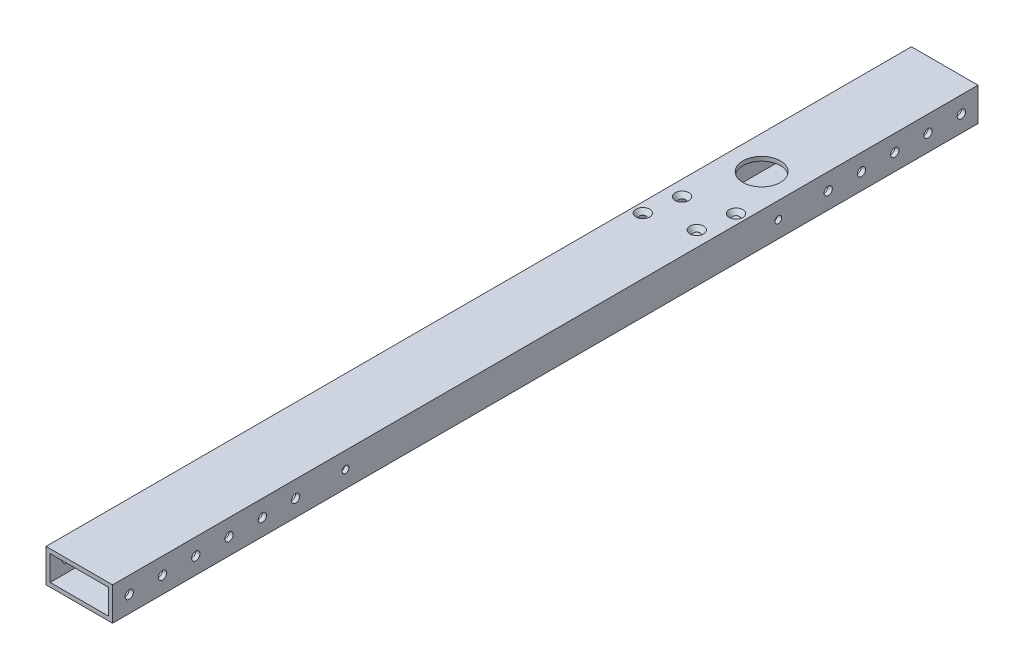
SolidWorks part; units mm, degrees
material "6061 Alloy"
ref_plane "Front Plane" through (0, 0, 0) normal (0, 0, 1) x (1, 0, 0)
ref_plane "Top Plane" through (0, 0, 0) normal (0, 1, 0) x (1, 0, 0)
ref_plane "Right Plane" through (0, 0, 0) normal (1, 0, 0) x (0, 0, -1)
sketch "Sketch1" plane through (0, 0, 0) normal (0, 0, 1) x (1, 0, 0)
  line L0 (-22.225, 9.525) -> (22.225, 9.525)
  line L2 (-25.4, 12.7) -> (25.4, 12.7)
  line L3 (-25.4, 12.7) -> (-25.4, -12.7)
  line L4 (-25.4, -12.7) -> (25.4, -12.7)
  line L5 (25.4, 12.7) -> (25.4, -12.7)
  line L10 (22.225, 9.525) -> (22.225, -9.525)
  line L11 (-22.225, -9.525) -> (22.225, -9.525)
  line L12 (-22.225, 9.525) -> (-22.225, -9.525)
  point P12 (0, 12.7)
  point P14 (25.4, 0)
  dimension "Wall Thickness" = 3.175
  dimension "Outside Width" = 50.8
  dimension "Outside Height" = 25.4
  dimension "Inside Height" = 19.05
  dimension "Inside Width" = 44.45
sketch "Sketch2" plane through (0, 0, 0) normal (1, 0, 0) x (0, 0, -1)
  line L0 (330.2, 0) -> (-330.2, 0)
  point P4 (0, 0)
  point P7 (-330.2, 0)
  point P10 (330.2, 0)
  dimension "Length" = 660.4
sketch "Sketch3" plane through (0, 0, 0) normal (0, 0, 1) x (1, 0, 0)
  line L21 (25.4, 12.7) -> (-25.4, 12.7)
  line L22 (25.4, -12.7) -> (25.4, 12.7)
  line L23 (-25.4, -12.7) -> (25.4, -12.7)
  line L24 (-25.4, 12.7) -> (-25.4, -12.7)
  line L25 (25.4, 12.7) -> (-25.4, 12.7)
  line L26 (25.4, -12.7) -> (25.4, 12.7)
  line L27 (-25.4, -12.7) -> (25.4, -12.7)
  line L28 (-25.4, 12.7) -> (-25.4, -12.7)
  line L29 (22.225, 9.525) -> (-22.225, 9.525)
  line L30 (22.225, -9.525) -> (22.225, 9.525)
  line L31 (-22.225, -9.525) -> (22.225, -9.525)
  line L32 (-22.225, 9.525) -> (-22.225, -9.525)
  line L33 (22.225, 9.525) -> (-22.225, 9.525)
  line L34 (22.225, -9.525) -> (22.225, 9.525)
  line L35 (-22.225, -9.525) -> (22.225, -9.525)
  line L36 (-22.225, 9.525) -> (-22.225, -9.525)
  dimension "D1" = 0
  dimension "D2" = 0
extrude "Boss-Extrude1" add sketch "Sketch3" along normal up to vertex (330.2 mm away) and the other way up to vertex (330.2 mm away) up to point (0, 0, 330.2) other way up to point (0, 0, -330.2)
sketch "Drawing Reference" plane through (0, 0, 0) normal (1, 0, 0) x (0, 0, -1)
  line L0 (-330.2, 0) -> (330.2, 0) construction
  line L1 (0, -12.7) -> (0, 12.7) construction
  line L2 (-330.2, -12.7) -> (330.2, -12.7) construction
  line L5 (-330.2, 12.7) -> (330.2, 12.7) construction
  point P7 (-293.624, 0)
  point P8 (293.624, 0)
  dimension "D1" = 36.576
sketch "Sketch5" plane through (25.4, 0, 0) normal (1, 0, 0) x (0, 0, -1)
  line L2 (-266.7, 0) -> (-241.3, 0)
  line L3 (-241.3, 0) -> (-215.9, 0)
  line L4 (-215.9, 0) -> (-190.5, 0)
  line L5 (-317.5, 0) -> (-330.2, 0)
  line L6 (-330.2, -12.7) -> (-330.2, 12.7) construction
  line L7 (-317.5, 0) -> (-292.1, 0)
  line L8 (-292.1, 0) -> (-266.7, 0)
sketch "Sketch8" plane through (25.4, 0, 0) normal (1, 0, 0) x (0, 0, -1)
  line L0 (330.2, 0) -> (292.1, 0)
  line L1 (330.2, -12.7) -> (330.2, 12.7) construction
  line L2 (292.1, 0) -> (266.7, 0)
  line L3 (266.7, 0) -> (241.3, 0)
  line L4 (241.3, 0) -> (215.9, 0)
  line L5 (330.2, 0) -> (317.5, 0)
hole_wizard "1/4 (0.25) Diameter Hole3" positions "Sketch12" profile "Sketch13" hole size "1/4" standard "ANSI Inch" end condition through all
sketch "Sketch12" plane through (-25.4, 0, 0) normal (-1, 0, 0) x (0, 0, 1)
  point P4 (-317.5, 0)
sketch "Sketch13" plane through (-25.4, 0, -317.5) normal (0, 1, 0) x (0, 0, 1)
  line L0 (0, 0) -> (0, 50.8)
  line L1 (0, 50.8) -> (3.175, 50.8)
  line L2 (3.175, 50.8) -> (3.175, 0)
  line L5 (3.175, 0) -> (0, 0)
  line L11 (0, -6.35) -> (0, 107.95) construction
  dimension "Thru Hole Dia." = 6.35
  dimension "Thru Hole Depth" = 50.8
hole_wizard "1/4 (0.25) Diameter Hole4" positions "Sketch14" profile "Sketch15" hole size "1/4" standard "ANSI Inch" end condition through all
sketch "Sketch14" plane through (-25.4, 0, 0) normal (-1, 0, 0) x (0, 0, 1)
  point P0 (292.1, 0)
  point P3 (317.5, 0)
sketch "Sketch15" plane through (-25.4, 0, 292.1) normal (0, 1, 0) x (0, 0, 1)
  line L0 (0, 0) -> (0, 50.8)
  line L1 (0, 50.8) -> (3.175, 50.8)
  line L2 (3.175, 50.8) -> (3.175, 0)
  line L5 (3.175, 0) -> (0, 0)
  line L11 (0, -6.35) -> (0, 107.95) construction
  dimension "Thru Hole Dia." = 6.35
  dimension "Thru Hole Depth" = 50.8
hole_wizard "1/4 (0.25) Diameter Hole5" positions "Sketch17" profile "Sketch18" hole size "1/4" standard "ANSI Inch" end condition through all
sketch "Sketch17" plane through (25.4, 0, 0) normal (1, 0, 0) x (0, 0, -1)
  point P0 (292.1, 0)
  point P3 (266.7, 0)
sketch "Sketch18" plane through (25.4, 0, -292.1) normal (0, 1, 0) x (0, 0, -1)
  line L0 (0, 0) -> (0, 50.8)
  line L1 (0, 50.8) -> (3.175, 50.8)
  line L2 (3.175, 50.8) -> (3.175, 0)
  line L5 (3.175, 0) -> (0, 0)
  line L11 (0, -6.35) -> (0, 107.95) construction
  dimension "Thru Hole Dia." = 6.35
  dimension "Thru Hole Depth" = 50.8
hole_wizard "1/4 (0.25) Diameter Hole6" positions "Sketch19" profile "Sketch20" hole size "1/4" standard "ANSI Inch" end condition through all
sketch "Sketch19" plane through (25.4, 0, 0) normal (1, 0, 0) x (0, 0, -1)
  point P0 (215.9, 0)
  point P3 (241.3, 0)
sketch "Sketch20" plane through (25.4, 0, -215.9) normal (0, 1, 0) x (0, 0, -1)
  line L0 (0, 0) -> (0, 50.8)
  line L1 (0, 50.8) -> (3.175, 50.8)
  line L2 (3.175, 50.8) -> (3.175, 0)
  line L5 (3.175, 0) -> (0, 0)
  line L11 (0, -6.35) -> (0, 107.95) construction
  dimension "Thru Hole Dia." = 6.35
  dimension "Thru Hole Depth" = 50.8
hole_wizard "1/4 (0.25) Diameter Hole7" positions "Sketch21" profile "Sketch22" hole size "1/4" standard "ANSI Inch" end condition through all
sketch "Sketch21" plane through (25.4, 0, 0) normal (1, 0, 0) x (0, 0, -1)
  point P0 (-190.5, 0)
  point P3 (-215.9, 0)
sketch "Sketch22" plane through (25.4, 0, 190.5) normal (0, 1, 0) x (0, 0, -1)
  line L0 (0, 0) -> (0, 50.8)
  line L1 (0, 50.8) -> (3.175, 50.8)
  line L2 (3.175, 50.8) -> (3.175, 0)
  line L5 (3.175, 0) -> (0, 0)
  line L11 (0, -6.35) -> (0, 107.95) construction
  dimension "Thru Hole Dia." = 6.35
  dimension "Thru Hole Depth" = 50.8
hole_wizard "1/4 (0.25) Diameter Hole8" positions "Sketch23" profile "Sketch24" hole size "1/4" standard "ANSI Inch" end condition through all
sketch "Sketch23" plane through (25.4, 0, 0) normal (1, 0, 0) x (0, 0, -1)
  point P0 (-266.7, 0)
  point P3 (-241.3, 0)
sketch "Sketch24" plane through (25.4, 0, 266.7) normal (0, 1, 0) x (0, 0, -1)
  line L0 (0, 0) -> (0, 50.8)
  line L1 (0, 50.8) -> (3.175, 50.8)
  line L2 (3.175, 50.8) -> (3.175, 0)
  line L5 (3.175, 0) -> (0, 0)
  line L11 (0, -6.35) -> (0, 107.95) construction
  dimension "Thru Hole Dia." = 6.35
  dimension "Thru Hole Depth" = 50.8
sketch "Sketch25" plane through (25.4, 0, 0) normal (1, 0, 0) x (0, 0, -1)
  line L0 (-190.5, 0) -> (-152.4, 0)
  line L1 (215.9, 0) -> (177.8, 0)
hole_wizard "13/64 (0.20313) Diameter Hole1" positions "Sketch26" profile "Sketch27" hole size "13/64" standard "ANSI Inch" end condition through all
sketch "Sketch26" plane through (25.4, 0, 0) normal (1, 0, 0) x (0, 0, -1)
  point P0 (-152.4, 0)
  point P3 (177.8, 0)
sketch "Sketch27" plane through (25.4, 0, 152.4) normal (0, 1, 0) x (0, 0, -1)
  line L0 (0, 0) -> (0, 50.8)
  line L1 (0, 50.8) -> (2.5798, 50.8)
  line L2 (2.5798, 50.8) -> (2.5798, 0)
  line L5 (2.5798, 0) -> (0, 0)
  line L11 (0, -6.35) -> (0, 107.95) construction
  dimension "Thru Hole Dia." = 5.1595
  dimension "Thru Hole Depth" = 50.8
sketch "Sketch28" plane through (-25.4, 0, 0) normal (-1, 0, 0) x (0, 0, 1)
  line L0 (103.1875, 0) -> (77.7875, 0)
  line L1 (-103.1875, 0) -> (-128.5875, 0)
hole_wizard "1/2 (0.5) Diameter Hole1" positions "Sketch29" profile "Sketch30" hole size "1/2" standard "ANSI Inch"
sketch "Sketch29" plane through (-25.4, 0, 0) normal (-1, 0, 0) x (0, 0, 1)
  point P1 (-591.3016, -480.8022)
  point P3 (-103.1875, 0)
  point P6 (77.7875, 0)
  point P9 (103.1875, 0)
  point P13 (-128.5875, 0)
sketch "Sketch30" plane through (-25.4, -480.8022, -591.3016) normal (0, 1, 0) x (0, 0, 1)
  line L0 (0, 0) -> (0, 10.1655)
  line L1 (0, 10.1655) -> (6.35, 6.35)
  line L2 (6.35, 6.35) -> (6.35, 0)
  line L5 (6.35, 0) -> (0, 0)
  line L10 (0, 10.1655) -> (-6.35, 6.35) construction
  line L11 (0, -6.35) -> (0, 107.95) construction
  dimension "Hole Dia." = 12.7
  dimension "Hole Depth" = 6.35
  dimension "Drill Angle" = 118
sketch "Sketch31" plane through (0, -12.7, 0) normal (0, -1, 0) x (1, 0, 0)
  line L0 (-25.4, -190.5081) -> (25.4, -190.5081) construction
  line L1 (-25.4, 330.2) -> (-25.4, -330.2) construction
  line L2 (25.4, 330.2) -> (25.4, -330.2) construction
  line L3 (0, -190.5081) -> (7.7911, -164.2057) construction
  line L4 (-25.4058, -154.3724) -> (575.1053, -332.2518) construction
  line L6 (7.7911, -164.2057) -> (10.4085, -164.981) construction
  circle A0 centre (0, -190.5081) radius 14.2875
  dimension "D2" = 28.575
  dimension "D1" = 27.432
extrude "Cut-Extrude1" cut sketch "Sketch31" against normal through all
sketch "Sketch32" plane through (0, -12.7, 0) normal (0, -1, 0) x (1, 0, 0)
  line L1 (17.9252, -153.0349) -> (13.8132, -127.1804) construction
  line L2 (-13.8248, -143.6302) -> (17.9252, -153.0349) construction
  line L3 (-17.9368, -117.7756) -> (13.8132, -127.1804) construction
  line L4 (-13.8248, -143.6302) -> (-17.9368, -117.7756) construction
hole_wizard "#10 Clearance Hole1" positions "Sketch33" profile "Sketch34" hole size "#10" standard "ANSI Inch" end condition through all
sketch "Sketch33" plane through (0, -12.7, 0) normal (0, -1, 0) x (-1, 0, 0)
  point P0 (13.8248, 143.6302)
  point P3 (17.9368, 117.7756)
  point P6 (-13.8132, 127.1804)
  point P9 (-17.9252, 153.0349)
sketch "Sketch34" plane through (-13.8248, -12.7, -143.6302) normal (1, 0, 0) x (0, 0, -1)
  line L0 (0, 0) -> (0, 25.4)
  line L1 (0, 25.4) -> (5.2197, 25.4)
  line L2 (2.4892, 22.2589) -> (2.4892, 0)
  line L5 (2.4892, 0) -> (0, 0)
  line L7 (5.2197, 25.4) -> (2.4892, 22.2589)
  line L8 (-5.2197, 25.4) -> (-2.4892, 22.2589) construction
  line L11 (0, -6.35) -> (0, 107.95) construction
  dimension "Thru Hole Dia." = 4.9784
  dimension "Thru Hole Depth" = 25.4
  dimension "Far C'Sink Dia." = 10.4394
  dimension "Far C'Sink Angle" = 82
equation "\"D1@Drawing Reference\"=\"Outside Width@Sketch1\" * 0.72"
